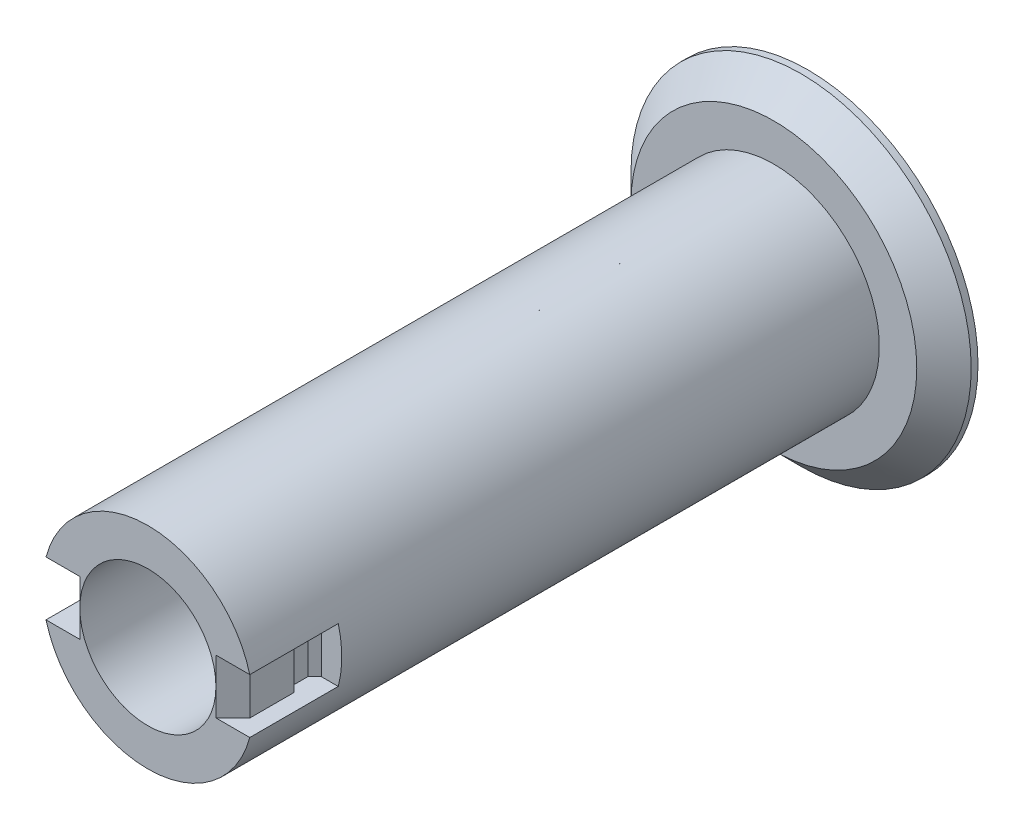
SolidWorks part; units mm, degrees
ref_plane "Front" through (0, 0, 0) normal (0, 0, 1) x (1, 0, 0)
ref_plane "Top" through (0, 0, 0) normal (0, 1, 0) x (1, 0, 0)
ref_plane "Right" through (0, 0, 0) normal (1, 0, 0) x (0, 0, -1)
sketch "Axle base sketch" plane through (0, 0, 0) normal (0, 0, 1) x (1, 0, 0)
  circle A0 centre (0, 0) radius 15.5
  dimension "D1" = 31
extrude "Axle" add sketch "Axle base sketch" along normal blind 92
sketch "Guard base" plane through (0, 0, 0) normal (0, 0, -1) x (-1, 0, 0)
  circle A0 centre (0, 0) radius 25
  dimension "D1" = 50
extrude "Guard" add sketch "Guard base" along normal blind 5
sketch "Inner axle hole base" plane through (0, 0, 92) normal (0, 0, 1) x (1, 0, 0)
  circle A0 centre (0, 0) radius 10
  dimension "D1" = 20
extrude "Inner axle hole" cut sketch "Inner axle hole base" against normal through all
sketch "Coupling tooth base" plane through (0, 0, 0) normal (0, 1, 0) x (1, 0, 0)
  line L0 (10, -92) -> (15.5, -92)
  line L1 (15.5, -92) -> (15.5, -79)
  line L2 (15.5, -92) -> (15.5, 0) construction
  line L3 (15.5, -79) -> (12.5, -79)
  line L5 (11.5, -82) -> (12.5, -83)
  line L6 (12.5, -83) -> (12.5, -89.5)
  line L7 (12.5, -89.5) -> (10, -92)
  line L9 (12.5, -79) -> (11.5, -80)
  line L10 (11.5, -80) -> (11.5, -82)
  dimension "D1" = 1
  dimension "D2" = 5.5
  dimension "D3" = 4
  dimension "D4" = 13
  dimension "D5" = 4
  dimension "D7" = 135
  dimension "D8" = 135
extrude "Coupling tooth hole" cut sketch "Coupling tooth base" against normal blind 4 and the other way blind 4 contours L9 L10 L5 L6 L7 L0 L1 L3 region at (13.7091, 0, 85.5933)
mirror "Coupling teeth" about plane through (0, 0, 0) normal (1, 0, 0) of "Coupling tooth hole"
chamfer "Uncoupling finger room" distance 4 angle 45 1 edges at (-25, 0, 0)
equation "\"32_92_spool_inner_diameter\"=32"
equation "\"D1@Axle base sketch\"=\"32_92_spool_inner_diameter\"- \"spool_inner_diameter_room\""
equation "\"spool_inner_diameter_room\"=1"
equation "\"32_92_spool_thickness\"=92"
equation "\"D1@Axle\"=\"32_92_spool_thickness\""
equation "\"32_92_guard_diameter\"=50"
equation "\"D1@Guard base\"=\"32_92_guard_diameter\""
equation "\"guard_thickness\"=5"
equation "\"D1@Guard\"=\"guard_thickness\""
equation "\"large_inner_axle_diameter\"=20"
equation "\"D1@Inner axle hole base\"=\"large_inner_axle_diameter\""
equation "\"32_92_coupling_tooth_height\"=13"
equation "\"D4@Coupling tooth base\"=\"32_92_coupling_tooth_height\""
equation "\"32_92_coupling_tooth_thickness_total\"=4"
equation "\"D3@Coupling tooth base\"=\"32_92_coupling_tooth_thickness_total\""
equation "\"32_92_coupling_tooth_protrusion\"=1"
equation "\"D1@Coupling tooth base\"=\"32_92_coupling_tooth_protrusion\""
equation "\"32_92_coupling_tooth_depth\"=8"
equation "\"D1@Coupling tooth hole\"=\"32_92_coupling_tooth_depth\"/2"
equation "\"D2@Coupling tooth hole\"=\"32_92_coupling_tooth_depth\"/2"
equation "\"32_92_coupling_tooth_base_thickness\"=5.5"
equation "\"D2@Coupling tooth base\"=\"32_92_coupling_tooth_base_thickness\""
equation "\"32_92_coupling_tooth_head_height\"=4"
equation "\"D5@Coupling tooth base\"=\"32_92_coupling_tooth_head_height\""
equation "\"D1@Uncoupling finger room\"=\"guard_thickness\"-1"
